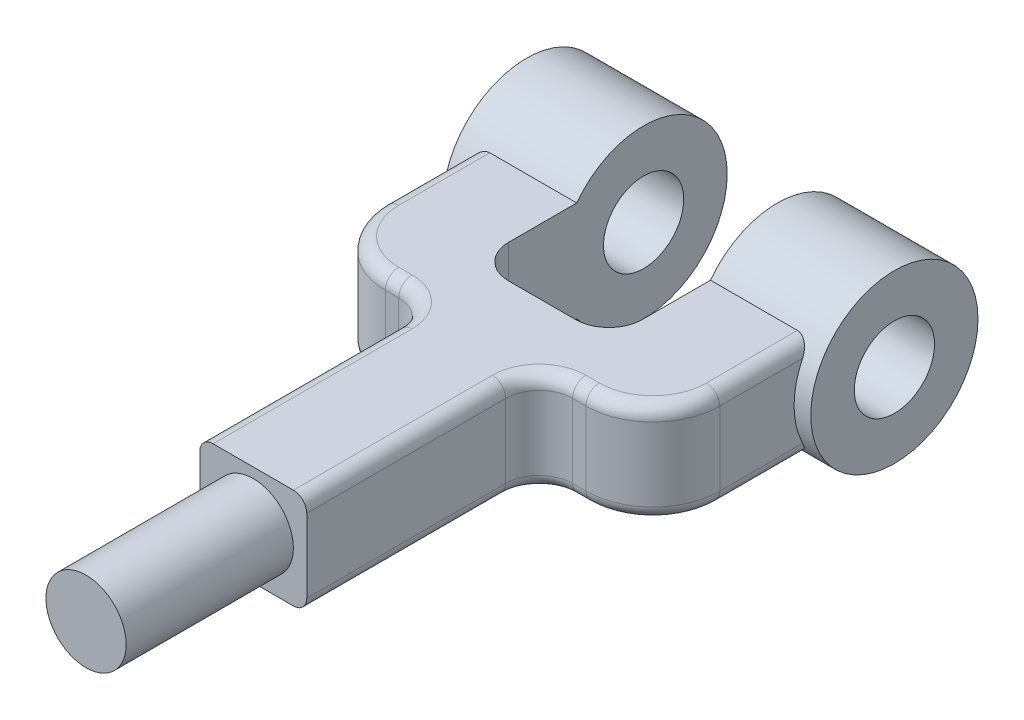
SolidWorks part; units mm, degrees
ref_plane "Front Plane" through (0, 0, 0) normal (0, 0, 1) x (1, 0, 0)
ref_plane "Top Plane" through (0, 0, 0) normal (0, 1, 0) x (1, 0, 0)
ref_plane "Right Plane" through (0, 0, 0) normal (1, 0, 0) x (0, 0, -1)
sketch "Sketch1" plane through (0, 0, 0) normal (0, 1, 0) x (1, 0, 0)
  line L0 (13, -11.2371) -> (15, -11.2371)
  line L1 (-5, -2.8096) -> (5, -2.8096)
  line L2 (-25, 2.3457) -> (-25, -1.2371)
  line L3 (-15, -11.2371) -> (-13, -11.2371)
  line L4 (25, 2.3457) -> (25, -1.2371)
  line L6 (-25, 2.3457) -> (-25, 30)
  line L7 (-25, 30) -> (-10, 30)
  line L8 (-10, 2.1904) -> (-10, 30)
  line L10 (25, 2.3457) -> (25, 30)
  line L11 (25, 30) -> (10, 30)
  line L12 (10, 2.1904) -> (10, 30)
  line L14 (-8, -16.2371) -> (-8, -45.9877)
  line L15 (-8, -45.9877) -> (8, -45.9877)
  line L16 (8, -16.2371) -> (8, -45.9877)
  arc A0 (15, -11.2371) -> (25, -1.2371) centre (15, -1.2371) ccw
  arc A1 (-25, -1.2371) -> (-15, -11.2371) centre (-15, -1.2371) ccw
  arc A2 (5, -2.8096) -> (10, 2.1904) centre (5, 2.1904) ccw
  arc A3 (-5, -2.8096) -> (-10, 2.1904) centre (-5, 2.1904) cw
  arc A4 (13, -11.2371) -> (8, -16.2371) centre (13, -16.2371) ccw
  arc A5 (-13, -11.2371) -> (-8, -16.2371) centre (-13, -16.2371) cw
  dimension "D10" = 10
  dimension "D11" = 5
  dimension "D12" = 5
  dimension "D1" = 50
  dimension "D2" = 25
  dimension "D3" = 16
  dimension "D4" = 8
  dimension "D5" = 15
  dimension "D6" = 15
  dimension "D7" = 30
  dimension "D8" = 30
extrude "Boss-Extrude1" add sketch "Sketch1" along normal mid plane 15 contours L10 L11 L12 A2 L1 A3 L8 L7 L6 L2 A1 L3 A5 L14 L15 L16 A4 L0 A0 L4
sketch "Sketch2" plane through (0, 0, 0) normal (1, 0, 0) x (0, 0, -1)
  circle A0 centre (22.3743, 0) radius 12.5
  circle A1 centre (22.3743, 0) radius 6
  dimension "D1" = 25
  dimension "D2" = 12
extrude "Boss-Extrude2" add sketch "Sketch2" along normal mid plane 55
extrude "Cut-Extrude1" cut sketch "Sketch2<3>" against normal through all both and the other way through all contours A1
sketch "Sketch2<3>" plane through (0, 0, 0) normal (1, 0, 0) x (0, 0, -1) same geometry as "Sketch2"
sketch "Sketch3" plane through (0, 0, 0) normal (0, 1, 0) x (1, 0, 0)
  line L0 (-10, 2.1904) -> (-10, 12.3743) construction
  line L1 (-10, 7.2824) -> (10, 7.2824)
  line L2 (-10, 7.2824) -> (-10, 34.8743)
  line L3 (-10, 34.8743) -> (10, 34.8743)
  line L4 (10, 7.2824) -> (10, 34.8743)
  line L5 (27.5, 34.8743) -> (-27.5, 34.8743) construction
extrude "Cut-Extrude2" cut sketch "Sketch3" against normal through all both and the other way through all contours L2 L3 L4 L1
fillet "Fillet1" radius 2 20 edges at (-25, -7.5, -5.5686) (-8, -7.5, 31.1124) (-9.4645, -7.5, 12.7015) (-14, -7.5, 11.2371) (8, -7.5, 31.1124) (9.4645, -7.5, 12.7015) (14, -7.5, 11.2371) (25, -7.5, -5.5686) (-25, 7.5, -5.5686) (-8, 7.5, 31.1124) (-9.4645, 7.5, 12.7015) (-14, 7.5, 11.2371) (8, 7.5, 31.1124) (9.4645, 7.5, 12.7015) (14, 7.5, 11.2371) (25, 7.5, -5.5686) (-22.0711, -7.5, 8.3081) (22.0711, -7.5, 8.3081) (-22.0711, 7.5, 8.3081) (22.0711, 7.5, 8.3081)
sketch "Sketch4" plane through (0, 0, 45.9877) normal (0, 0, 1) x (1, 0, 0)
  circle A0 centre (0, 0) radius 6
  dimension "D1" = 12
extrude "Boss-Extrude3" add sketch "Sketch4" along normal blind 25
